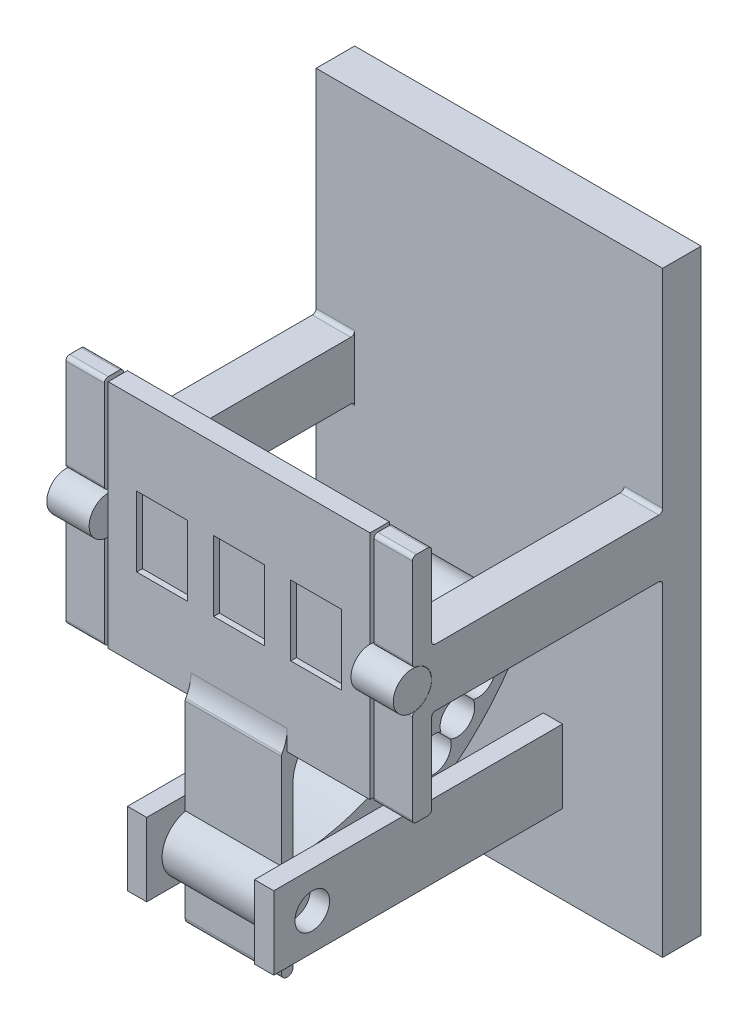
SolidWorks part; units mm, degrees
ref_plane "Front Plane" through (0, 0, 0) normal (1, 0, 0) x (0, 1, 0)
ref_plane "Top Plane" through (0, 0, 0) normal (0, 0, 1) x (0, 1, 0)
ref_plane "Right Plane" through (0, 0, 0) normal (0, 1, 0) x (-1, 0, 0)
sketch "Sketch1" plane through (0, 0, 0) normal (0, 0, 1) x (0, 1, 0)
  line L1 (-62.5, -45) -> (62.5, -45)
  line L2 (-62.5, -45) -> (-62.5, 45)
  line L3 (-62.5, 45) -> (62.5, 45)
  line L4 (62.5, -45) -> (62.5, 45)
  line L5 (0, 45) -> (0, -45) construction
  line L6 (-62.5, 0) -> (62.5, 0) construction
  point P0 (0, 0)
  dimension "D1" = 90
  dimension "D2" = 125
extrude "Boss-Extrude1" add sketch "Sketch1" along normal blind 10 contours L2 L1 L4 L3
sketch "Sketch3" plane through (0, 0, 0) normal (1, 0, 0) x (0, 1, 0)
  line L0 (0, 0) -> (0, 50000) construction
  line L4 (5.9161, 75) -> (7.5, 75)
  line L5 (-7.5, 75) -> (-5.9161, 75)
  line L6 (-7.5, 0) -> (-7.5, 69)
  line L7 (7.5, 0) -> (7.5, 69)
  line L8 (-7.5, 0) -> (7.5, 0)
  line L10 (7.5, 75) -> (7.5, 70) construction
  line L11 (8.5, 70) -> (29.144, 70)
  line L12 (7.5, 75) -> (29.144, 75)
  line L13 (30.144, 74) -> (30.144, 71)
  line L15 (-8.5, 70) -> (-29.144, 70)
  line L16 (-30.144, 74) -> (-30.144, 71)
  line L17 (-7.5, 75) -> (-29.144, 75)
  circle A0 centre (0, 75) radius 62.5 construction
  arc A2 (-4.9301, 74.1667) -> (-5.9161, 75) centre (-5.9161, 74) ccw
  arc A3 (5.9161, 75) -> (4.9301, 74.1667) centre (5.9161, 74) ccw
  arc A4 (29.144, 70) -> (30.144, 71) centre (29.144, 71) ccw
  arc A5 (30.144, 74) -> (29.144, 75) centre (29.144, 74) ccw
  arc A6 (8.5, 70) -> (7.5, 69) centre (8.5, 69) ccw
  arc A7 (-8.5, 70) -> (-7.5, 69) centre (-8.5, 69) cw
  arc A8 (-29.144, 70) -> (-30.144, 71) centre (-29.144, 71) cw
  arc A9 (-30.144, 74) -> (-29.144, 75) centre (-29.144, 74) cw
  arc A10 (-4.9301, 74.1667) -> (4.9301, 74.1667) centre (0, 75) ccw
  point P18 (-5, 75)
  point P21 (5, 75)
  dimension "D2" = 125
  dimension "D9" = 1
  dimension "D1" = 7.5
  dimension "D3" = 7.5
extrude "Boss-Extrude2" add sketch "Sketch3" along normal mid plane 70
sketch "Sketch5" plane through (0, 0, 0) normal (1, 0, 0) x (0, 1, 0)
  line L0 (0, -49.5) -> (0, 49.5) construction
  line L2 (-8.5, 10) -> (8.5, 10)
  line L9 (-7.5, 69) -> (-7.5, 10)
  line L10 (-7.5, 10) -> (7.5, 10)
  line L11 (7.5, 10) -> (7.5, 69)
  line L12 (8.5, 70) -> (29.144, 70)
  line L13 (30.144, 71) -> (30.144, 74)
  line L14 (29.144, 75) -> (5.9161, 75)
  line L15 (-5.9161, 75) -> (-29.144, 75)
  line L16 (-30.144, 74) -> (-30.144, 71)
  line L17 (-29.144, 70) -> (-8.5, 70)
  line L18 (-7.5, 69) -> (-7.5, 11)
  line L19 (-7.5, 10) -> (7.5, 10)
  line L20 (7.5, 11) -> (7.5, 69)
  line L21 (8.5, 70) -> (29.144, 70)
  line L22 (30.144, 71) -> (30.144, 74)
  line L23 (29.144, 75) -> (5.9161, 75)
  line L24 (-5.9161, 75) -> (-29.144, 75)
  line L25 (-30.144, 74) -> (-30.144, 71)
  line L26 (-29.144, 70) -> (-8.5, 70)
  arc A0 (8.5, 10) -> (7.5, 11) centre (8.5, 11) cw
  arc A1 (-8.5, 10) -> (-7.5, 11) centre (-8.5, 11) ccw
  arc A9 (8.5, 70) -> (7.5, 69) centre (8.5, 69) ccw
  arc A10 (29.144, 70) -> (30.144, 71) centre (29.144, 71) ccw
  arc A11 (30.144, 74) -> (29.144, 75) centre (29.144, 74) ccw
  arc A12 (5.9161, 75) -> (4.9301, 74.1667) centre (5.9161, 74) ccw
  arc A13 (-4.9301, 74.1667) -> (4.9301, 74.1667) centre (0, 75) ccw
  arc A14 (-4.9301, 74.1667) -> (-5.9161, 75) centre (-5.9161, 74) ccw
  arc A15 (-29.144, 75) -> (-30.144, 74) centre (-29.144, 74) ccw
  arc A16 (-30.144, 71) -> (-29.144, 70) centre (-29.144, 71) ccw
  arc A17 (-7.5, 69) -> (-8.5, 70) centre (-8.5, 69) ccw
  arc A18 (8.5, 70) -> (7.5, 69) centre (8.5, 69) ccw
  arc A19 (29.144, 70) -> (30.144, 71) centre (29.144, 71) ccw
  arc A20 (30.144, 74) -> (29.144, 75) centre (29.144, 74) ccw
  arc A21 (5.9161, 75) -> (4.9301, 74.1667) centre (5.9161, 74) ccw
  arc A22 (-4.9301, 74.1667) -> (4.9301, 74.1667) centre (0, 75) ccw
  arc A23 (-4.9301, 74.1667) -> (-5.9161, 75) centre (-5.9161, 74) ccw
  arc A24 (-29.144, 75) -> (-30.144, 74) centre (-29.144, 74) ccw
  arc A25 (-30.144, 71) -> (-29.144, 70) centre (-29.144, 71) ccw
  arc A26 (-7.5, 69) -> (-8.5, 70) centre (-8.5, 69) ccw
  dimension "D3" = 1
  dimension "D1" = 0
extrude "Boss-Extrude3" add sketch "Sketch5" along normal mid plane 90 contours A26 L18 A1 L2 A0 L20 A18 L21 A19 L22 A20 L23 A21 A22 A23 L24 A24 L25 A25 L26
sketch "Sketch7" plane through (0, 7.5, 0) normal (0, 1, 0) x (-1, 0, 0)
  line L0 (0, 10) -> (0, 75)
  line L1 (-45, 10) -> (45, 10) construction
  line L2 (-45, 75) -> (45, 75) construction
  line L4 (-35, 10) -> (35, 10)
  line L5 (-35, 10) -> (-35, 75)
  line L6 (-35, 75) -> (35, 75)
  line L7 (35, 10) -> (35, 75)
  line L8 (0, 75) -> (0, 10) construction
  line L9 (-35, 42.5) -> (35, 42.5) construction
  point P6 (0, 42.5)
  line M5 (45, 69) -> (-45, 69)
  line M7 (-45, 11) -> (45, 11)
  dimension "D1" = 65
  dimension "D2" = 70
extrude "Cut-Extrude3" cut sketch "Sketch7" against normal through all both and the other way through all contours L5 L0 M7 M5 | L7 L0 M7 M5 | L5 L4 L0 M7 | L4 L7 L0 M7 | L6 L5 L0 M5 | L7 L6 L0 M5
sketch "Sketch11" plane through (0, 0, 10) normal (0, 0, 1) x (1, 0, 0)
  line L1 (-45, -62.5) -> (45, -62.5)
  line L2 (-45, -62.5) -> (-45, -92.5)
  line L3 (-45, -92.5) -> (45, -92.5)
  line L4 (45, -62.5) -> (45, -92.5)
  dimension "D1" = 30
  dimension "D2" = 90
extrude "Boss-Extrude5" add sketch "Sketch11" against normal blind 10
sketch "Sketch13" plane through (0, 0, 10) normal (0, 0, 1) x (1, 0, 0)
  line L1 (-34, -30) -> (34, -30)
  line L2 (-34, -30) -> (-34, 30)
  line L3 (-34, 30) -> (34, 30)
  line L4 (34, -30) -> (34, 30)
  line L5 (0, 30) -> (0, -30) construction
  line L6 (-34, 0) -> (34, 0) construction
  point P0 (0, 0)
  dimension "D1" = 60
  dimension "D2" = 68
extrude "Boss-Extrude6" add sketch "Sketch13" along normal up to surface (65 mm away) contours L1 L4 L3 L2 up to face at (40, 17.5301, 75)
sketch "Sketch14" plane through (0, 30, 0) normal (0, 1, 0) x (-1, 0, 0)
  line L0 (-34, 10) -> (-34, 70)
  line L1 (-34, 70) -> (34, 70)
  line L2 (34, 75) -> (34, 10) construction
  line L3 (34, 70) -> (34, 10)
  line L4 (34, 10) -> (-34, 10)
  line M6 (-34, 75) -> (-34, 10)
  line M7 (-34, 10) -> (34, 10)
  line M8 (34, 10) -> (34, 75)
  dimension "D1" = 60
extrude "Cut-Extrude6" cut sketch "Sketch14" against normal through all both and the other way through all contours L1 M6 M7 M8
sketch "Sketch15" plane through (34, 0, 0) normal (1, 0, 0) x (0, 1, 0)
  line L0 (30, 75) -> (-30, 75) construction
  circle A0 centre (0, 75) radius 4.95
  dimension "D1" = 9.9
extrude "Boss-Extrude8" add sketch "Sketch15" along normal blind 11 contours A0
mirror "Mirror2" about plane through (0, 0, 0) normal (1, 0, 0) of "Boss-Extrude8"
sketch "Sketch17" plane through (0, 0, 75) normal (0, 0, 1) x (1, 0, 0)
  line L0 (13.4, -9.1) -> (13.4, 9.1)
  line L1 (-6.6, -9.1) -> (6.6, -9.1)
  line L2 (-6.6, -9.1) -> (-6.6, 9.1)
  line L3 (-6.6, 9.1) -> (6.6, 9.1)
  line L4 (6.6, -9.1) -> (6.6, 9.1)
  line L5 (0, 9.1) -> (0, -9.1) construction
  line L6 (-6.6, 0) -> (6.6, 0) construction
  line L7 (13.4, 9.1) -> (26.6, 9.1)
  line L8 (26.6, -9.1) -> (26.6, 9.1)
  line L9 (13.4, -9.1) -> (26.6, -9.1)
  line L10 (0, -75.625) -> (0, 75.625) construction
  line L11 (-13.4, -9.1) -> (-26.6, -9.1)
  line L12 (-26.6, -9.1) -> (-26.6, 9.1)
  line L13 (-13.4, 9.1) -> (-26.6, 9.1)
  line L14 (-13.4, -9.1) -> (-13.4, 9.1)
  point P0 (0, 0)
  dimension "D1" = 18.2
  dimension "D2" = 13.2
  dimension "D3" = 2
extrude "Cut-Extrude7" cut sketch "Sketch17" against normal blind 1.5 and the other way through all
sketch "Sketch19" plane through (0, 0, 0) normal (1, 0, 0) x (0, 1, 0)
  line L0 (0, 75) -> (-54.1266, 43.75) construction
  line L3 (-5.9161, 75) -> (-29.144, 75) construction
  line L4 (0, 75) -> (-62.5, 75) construction
  line L5 (0, 75) -> (-54.1644, 84.5506) construction
  circle A0 centre (0, 75) radius 62.5 construction
  circle A1 centre (-54.1266, 43.75) radius 4.5
  circle A2 centre (-49.5846, 36.9524) radius 4.5
  circle A3 centre (0, 75) radius 62.5 construction
  circle A4 centre (-44.1942, 30.8058) radius 4.5
  circle A5 centre (0, 75) radius 62.5 construction
  circle A6 centre (-38.0476, 25.4154) radius 4.5
  circle A7 centre (0, 75) radius 62.5 construction
  circle A8 centre (-31.25, 20.8734) radius 4.5
  circle A9 centre (0, 75) radius 62.5 construction
  circle A10 centre (-62.5, 75) radius 4.5
  arc A11 (-55, 75) -> (-27.5, 27.3686) centre (0, 75) ccw
  arc A12 (-70, 75) -> (-35, 14.3782) centre (0, 75) ccw
  arc A13 (-70, 75) -> (-55, 75) centre (-62.5, 75) cw
  arc A14 (-68.9365, 87.1554) -> (-25.9808, 10) centre (0, 75) ccw construction
  arc A15 (-54.1644, 84.5506) -> (-20.4135, 23.9286) centre (0, 75) ccw construction
  arc A16 (-35, 14.3782) -> (-27.5, 27.3686) centre (-31.25, 20.8734) ccw
  dimension "D1" = 125
  dimension "D3" = 9
  dimension "D6" = 9
  dimension "D8" = 55
  dimension "D2" = 30
  dimension "D7" = 10
  dimension "D4" = 5
extrude "Boss-Extrude10" add sketch "Sketch19" along normal mid plane 25 separate body
sketch "Sketch20" plane through (0, 0, 0) normal (1, 0, 0) x (0, 1, 0)
  line L0 (-30, 75) -> (-55, 75)
  line L1 (-30, 76.5) -> (-55, 76.5)
  line L2 (-30, 73.5) -> (-55, 73.5)
  line L3 (-55, 76.5) -> (-55, 73.5)
  line L4 (-30, 76.5) -> (-30, 73.5)
  arc A0 (-55, 75) -> (-27.5, 27.3686) centre (0, 75) ccw construction
  dimension "D1" = 1.5
  dimension "D2" = 1.5
extrude "Boss-Extrude12" add sketch "Sketch20" along normal mid plane 25 contours L4 L1 L3 L0 | L4 L0 L3 L2
sketch "Sketch21" plane through (0, 0, 10) normal (0, 0, 1) x (1, 0, 0)
  line L0 (12.5, -67) -> (12.5, -58) construction
  line L1 (-12.5, -58) -> (-12.5, -67) construction
  line L2 (12.5, -67) -> (12.5, -58)
  line L3 (-12.5, -58) -> (-12.5, -67)
  line L4 (14, -67) -> (14, -58)
  line L10 (14, -67) -> (14, -72)
  line L11 (14, -72) -> (19, -72)
  line L12 (14, -58) -> (14, -53)
  line L13 (14, -53) -> (19, -53)
  line L14 (19, -53) -> (19, -72)
  dimension "D1" = 1.5
  dimension "D2" = 5
  dimension "D3" = 5
  dimension "D4" = 5
extrude "Boss-Extrude13" add sketch "Sketch21" along normal blind 75 contours L14 L11 L10 L4 L12 L13
sketch "Sketch22" plane through (14, 0, 0) normal (-1, 0, 0) x (0, -1, 0)
  circle A0 centre (62.5, 75) radius 4.5 construction
  circle A1 centre (62.5, 75) radius 4.5
extrude "Cut-Extrude8" cut sketch "Sketch22" against normal blind 75
mirror "Mirror3" about plane through (0, 0, 0) normal (1, 0, 0) of "Cut-Extrude8", "Boss-Extrude13"
fillet "Fillet1" radius 10 2 edges at (0, -30, 73.5) (0, -30, 75)
fillet "Fillet5" radius 1 1 edges at (0, -30, 76.5)
sketch "Sketch23" plane through (0, 0, 0) normal (1, 0, 0) x (0, 1, 0)
  line L0 (-72, 76.5) -> (-79.1903, 76.5)
  line L3 (-79.1903, 73.5) -> (-72, 73.5)
  line L4 (-72, 85) -> (-72, 10) construction
  line L5 (-72, 76.5) -> (-72, 73.5)
  arc A0 (-79.1903, 76.5) -> (-79.1903, 73.5) centre (-79.1903, 75) ccw
  dimension "D1" = 3
extrude "Boss-Extrude14" add sketch "Sketch23" along normal mid plane 25 separate body contours A0 L3 L5 L0
sketch "Sketch24" plane through (0, -72, 0) normal (0, 1, 0) x (-1, 0, 0)
  line L4 (12.5, 73.5) -> (12.5, 76.5)
  line L5 (12.5, 76.5) -> (-12.5, 76.5)
  line L6 (-12.5, 76.5) -> (-12.5, 73.5)
  line L7 (-12.5, 73.5) -> (12.5, 73.5)
  line L8 (12.5, 73.5) -> (12.5, 76.5)
  line L9 (12.5, 76.5) -> (-12.5, 76.5)
  line L10 (-12.5, 76.5) -> (-12.5, 73.5)
  line L11 (-12.5, 73.5) -> (12.5, 73.5)
  dimension "D1" = 0
extrude "Boss-Extrude16" add sketch "Sketch24" along normal up to surface (5.2574 mm away) contours L8 L9 L10 L11 up to face at (12.5, -62.5, 70.5)
other "Save Bodies1"
other "Save Bodies2"
